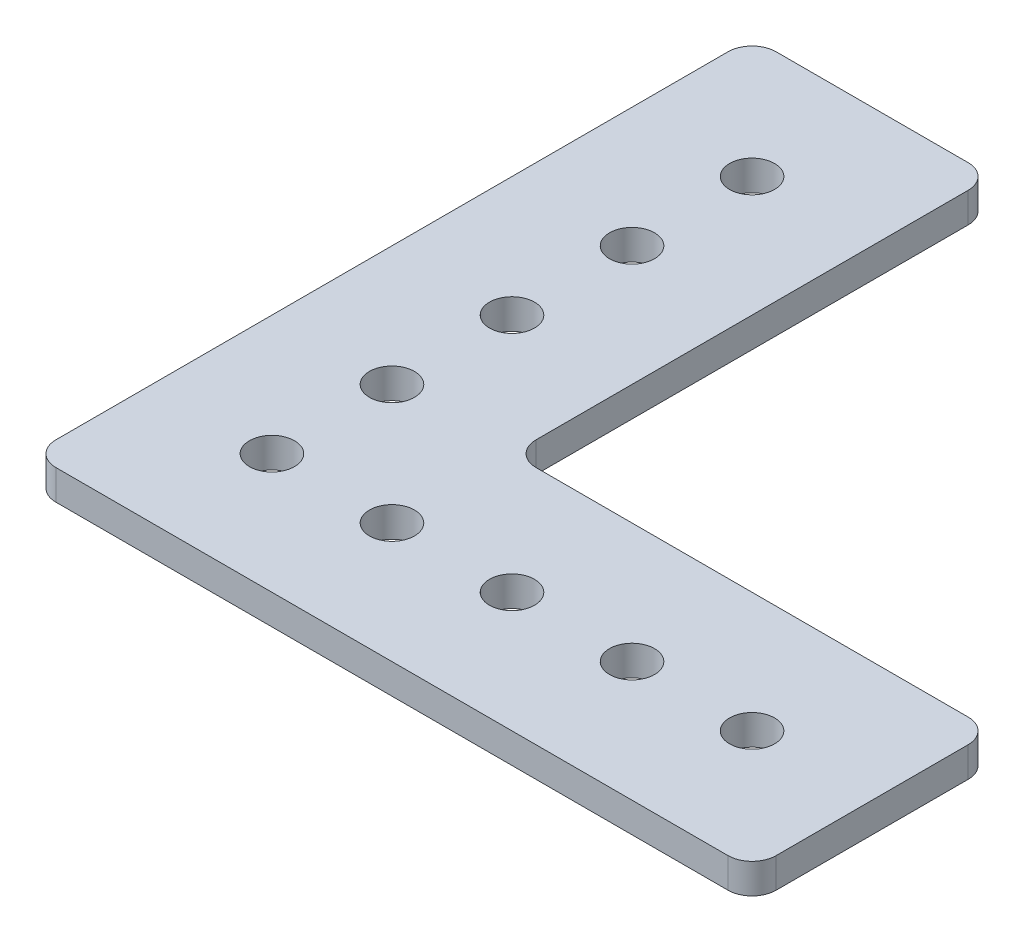
SolidWorks part; units mm, degrees
material "1060 Alloy"
ref_plane "Front Plane" through (0, 0, 0) normal (0, 0, 1) x (1, 0, 0)
ref_plane "Top Plane" through (0, 0, 0) normal (0, 1, 0) x (1, 0, 0)
ref_plane "Right Plane" through (0, 0, 0) normal (1, 0, 0) x (0, 0, -1)
sketch "Sketch1" plane through (0, 0, 0) normal (0, 1, 0) x (1, 0, 0)
  line L1 (2.54, 0) -> (25.4, 0)
  line L2 (0, 2.54) -> (0, 73.66)
  line L3 (2.54, 76.2) -> (22.86, 76.2)
  line L4 (25.4, 27.94) -> (25.4, 73.66)
  line L5 (0, 0) -> (73.66, 0)
  line L6 (0, 0) -> (0, 25.4)
  line L7 (27.94, 25.4) -> (73.66, 25.4)
  line L8 (76.2, 2.54) -> (76.2, 22.86)
  circle A0 centre (12.7, 12.7) radius 2.3813
  circle A1 centre (25.4, 12.7) radius 2.3813
  circle A2 centre (38.1, 12.7) radius 2.3812
  circle A3 centre (50.8, 12.7) radius 2.3812
  circle A4 centre (12.7, 25.4) radius 2.3813
  circle A5 centre (12.7, 38.1) radius 2.3812
  circle A6 centre (12.7, 50.8) radius 2.3812
  arc A7 (0, 2.54) -> (2.54, 0) centre (2.54, 2.54) ccw
  arc A8 (73.66, 0) -> (76.2, 2.54) centre (73.66, 2.54) ccw
  arc A9 (76.2, 22.86) -> (73.66, 25.4) centre (73.66, 22.86) ccw
  arc A10 (27.94, 25.4) -> (25.4, 27.94) centre (27.94, 27.94) cw
  arc A11 (25.4, 73.66) -> (22.86, 76.2) centre (22.86, 73.66) ccw
  arc A12 (0, 73.66) -> (2.54, 76.2) centre (2.54, 73.66) cw
  circle A13 centre (12.7, 63.5) radius 2.3812
  circle A14 centre (63.5, 12.7) radius 2.3813
  point P28 (76.2, 0)
  point P31 (76.2, 25.4)
  point P36 (25.4, 76.2)
  point P39 (0, 76.2)
  dimension "D5" = 4.7625
  dimension "D6" = 4.7625
  dimension "3/16" = 4.7625
  dimension "D8" = 4.7625
  dimension "D9" = 12.7
  dimension "D10" = 12.7
  dimension "D11" = 12.7
  dimension "D12" = 12.7
  dimension "D13" = 12.7
  dimension "D14" = 12.7
  dimension "D15" = 12.7
  dimension "D16" = 12.7
  dimension "D17" = 4.7625
  dimension "D18" = 12.7
  dimension "D19" = 4.7625
  dimension "D20" = 12.7
  dimension "D21" = 4.7625
  dimension "D22" = 12.7
  dimension "D23" = 12.7
  dimension "D24" = 12.7
  dimension "D25" = 12.7
  dimension "D26" = 2.54
  dimension "D27" = 4.7625
  dimension "D29" = 4.7625
  dimension "D1" = 76.2
  dimension "D2" = 76.2
  dimension "D3" = 25.4
  dimension "D4" = 25.4
  dimension "D28" = 12.7
  dimension "D30" = 12.7
extrude "Boss-Extrude1" add sketch "Sketch1" along normal blind 3.175 contours A12 L2 A7 L1 L5 A8 L8 A9 L7 A10 L4 A11 L3 A6 A5 A4 A3 A2 A1 A0 region at (1.5059, 0, -1.5059)
